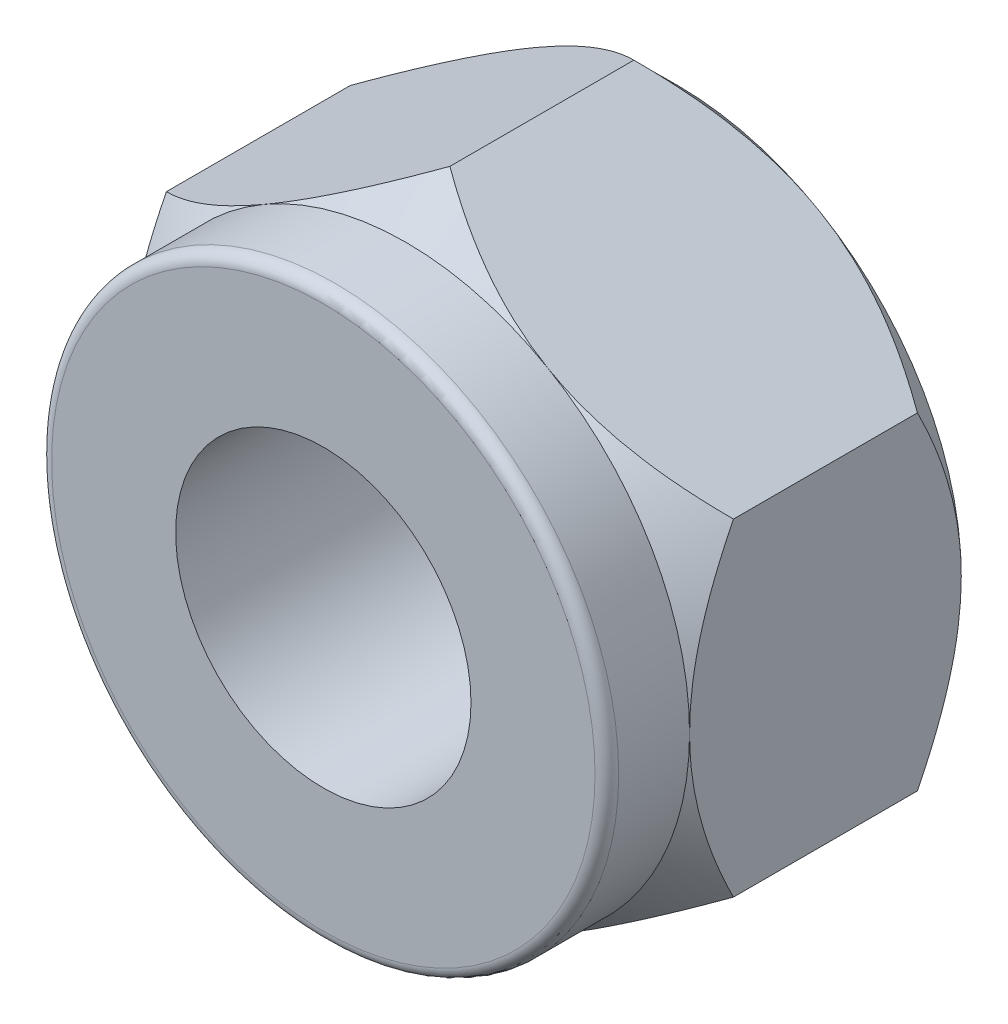
SolidWorks part; units mm, degrees
material "AISI 304"
ref_plane "前视基准面" through (0, 0, 0) normal (0, 0, 1) x (1, 0, 0)
ref_plane "上视基准面" through (0, 0, 0) normal (0, 1, 0) x (1, 0, 0)
ref_plane "右视基准面" through (0, 0, 0) normal (1, 0, 0) x (0, 0, -1)
sketch "草图1" plane through (0, 0, 0) normal (0, 0, 1) x (1, 0, 0)
  line L0 (0, 2.7713) -> (-2.4, 1.3856)
  line L1 (-2.4, 1.3856) -> (-2.4, -1.3856)
  line L2 (-2.4, -1.3856) -> (0, -2.7713)
  line L3 (0, -2.7713) -> (2.4, -1.3856)
  line L4 (2.4, -1.3856) -> (2.4, 1.3856)
  line L5 (2.4, 1.3856) -> (0, 2.7713)
  dimension "D1" = 4.8
extrude "凸台-拉伸1" add sketch "草图1" along normal blind 2.3
sketch "草图2" plane through (0, 0, 2.3) normal (0, 0, 1) x (1, 0, 0)
  circle A0 centre (0, 0) radius 2.4
extrude "凸台-拉伸2" add sketch "草图2" along normal blind 0.7
sketch "草图3" plane through (0, 0, 3) normal (0, 0, 1) x (1, 0, 0)
  circle A0 centre (0, 0) radius 1.25
  dimension "D1" = 2.5
extrude "切除-拉伸1" cut sketch "草图3" against normal through all
sketch "草图4" plane through (0, 0, 0) normal (0, 0, -1) x (-1, 0, 0)
  circle A0 centre (0, 0) radius 2.4
extrude "切除-拉伸10" cut sketch "草图4" against normal blind 1 draft 45 flip side to cut
extrude "切除-拉伸11" cut sketch "草图2<4>" against normal blind 1 draft 45 flip side to cut
sketch "草图2<4>" plane through (0, 0, 2.3) normal (0, 0, 1) x (1, 0, 0) same geometry as "草图2"
fillet "圆角1" radius 0.1 1 edges at (2.4, 0, 3)
